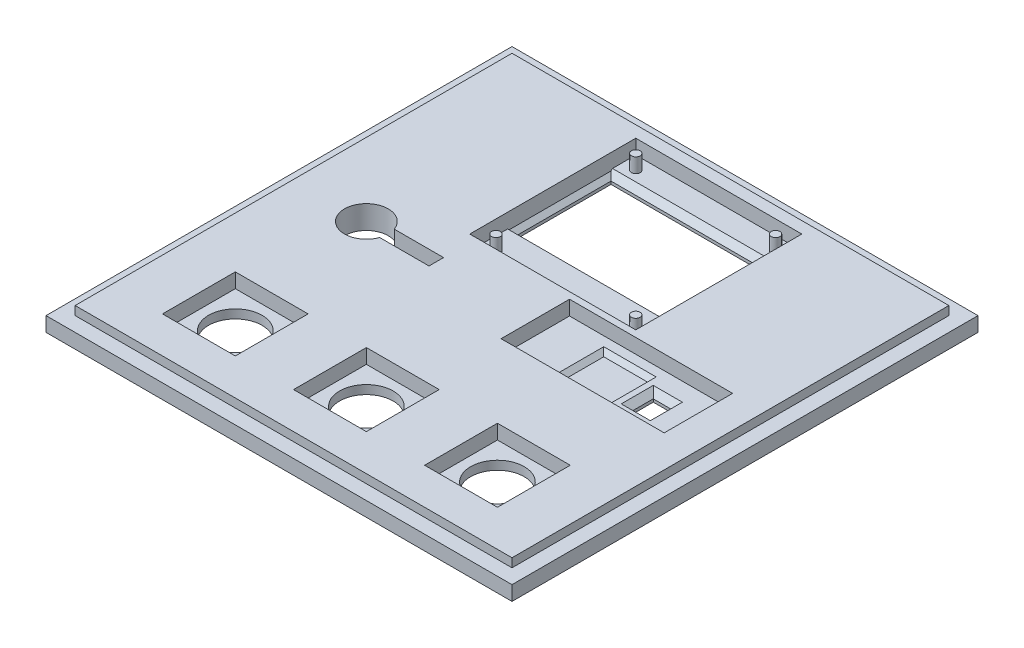
SolidWorks part; units mm, degrees
ref_plane "Ebene vorne" through (0, 0, 0) normal (0, 0, 1) x (1, 0, 0)
ref_plane "Ebene oben" through (0, 0, 0) normal (0, 1, 0) x (1, 0, 0)
ref_plane "Ebene rechts" through (0, 0, 0) normal (1, 0, 0) x (0, 0, -1)
sketch "Sketch1" plane through (0, 0, 0) normal (0, 1, 0) x (1, 0, 0)
  line L0 (0, -1000) -> (0, 49000) construction
  line L1 (-40, -40) -> (40, -40)
  line L2 (-40, -40) -> (-40, 40)
  line L3 (-40, 40) -> (40, 40)
  line L4 (40, -40) -> (40, 40)
  line L5 (-40, -40) -> (40, 40) construction
  line L6 (-40, 40) -> (40, -40) construction
  line L7 (-13.5, 30.5) -> (13.5, 30.5)
  line L8 (-13.5, 30.5) -> (-13.5, 14.5)
  line L9 (-13.5, 14.5) -> (13.5, 14.5)
  line L10 (13.5, 30.5) -> (13.5, 14.5)
  line L11 (-13.5, 30.5) -> (13.5, 14.5) construction
  line L12 (-13.5, 14.5) -> (13.5, 30.5) construction
  line L13 (22.5, 1.75) -> (25.5, 1.75)
  line L14 (22.5, 1.75) -> (22.5, -1.75)
  line L15 (22.5, -1.75) -> (25.5, -1.75)
  line L16 (25.5, 1.75) -> (25.5, -1.75)
  line L17 (22.5, 1.75) -> (25.5, -1.75) construction
  line L18 (22.5, -1.75) -> (25.5, 1.75) construction
  line L20 (-25.75, -28.25) -> (-19.25, -28.25) construction
  line L21 (-25.75, -28.25) -> (-25.75, -21.75) construction
  line L22 (-25.75, -21.75) -> (-19.25, -21.75) construction
  line L23 (-19.25, -28.25) -> (-19.25, -21.75) construction
  line L24 (-25.75, -28.25) -> (-19.25, -21.75) construction
  line L25 (-25.75, -21.75) -> (-19.25, -28.25) construction
  circle A0 centre (-25, 0) radius 3.75
  circle A1 centre (-22.5, -25) radius 4.5962
  circle A2 centre (0, -25) radius 4.5962
  circle A3 centre (22.5, -25) radius 4.5962
  point P0 (0, 0)
  point P8 (0, 22.5)
  point P13 (24, 0)
  dimension "D1" = 7.5
  dimension "D9" = 6.5
  dimension "D2" = 25
  dimension "D3" = 27
  dimension "D4" = 16
  dimension "D5" = 22.5
  dimension "D6" = 3.5
  dimension "D7" = 3
  dimension "D8" = 24
  dimension "D10" = 6.5
  dimension "D11" = 25
  dimension "D12" = 45
  dimension "D13" = 80
  dimension "D14" = 80
extrude "Boss-Extrude1" add sketch "Sketch1" along normal blind 2.5
sketch "Sketch2" plane through (0, 2.5, 0) normal (0, 1, 0) x (1, 0, 0)
  line L14 (-37.5, -37.5) -> (37.5, -37.5)
  line L15 (37.5, -37.5) -> (37.5, 37.5)
  line L16 (37.5, 37.5) -> (-37.5, 37.5)
  line L17 (-37.5, 37.5) -> (-37.5, -37.5)
  line L18 (-37.5, -37.5) -> (37.5, -37.5)
  line L19 (37.5, -37.5) -> (37.5, 37.5)
  line L20 (37.5, 37.5) -> (-37.5, 37.5)
  line L21 (-37.5, 37.5) -> (-37.5, -37.5)
  line L60 (-13.5, 14.5) -> (13.5, 14.5) construction
  line L65 (-13.5, 30.5) -> (-13.5, 14.5) construction
  line L71 (13.5, 30.5) -> (-13.5, 30.5) construction
  line L78 (13.5, 14.5) -> (13.5, 30.5) construction
  line L94 (-13.5, 14.5) -> (13.5, 14.5)
  line L95 (13.5, 14.5) -> (13.5, 30.5)
  line L96 (13.5, 30.5) -> (-13.5, 30.5)
  line L97 (-13.5, 30.5) -> (-13.5, 14.5)
  line L106 (25.5, 1.75) -> (22.5, 1.75)
  line L107 (25.5, -1.75) -> (25.5, 1.75)
  line L108 (22.5, -1.75) -> (25.5, -1.75)
  line L109 (22.5, 1.75) -> (22.5, -1.75)
  line L110 (25.5, 1.75) -> (22.5, 1.75)
  line L111 (25.5, -1.75) -> (25.5, 1.75)
  line L112 (22.5, -1.75) -> (25.5, -1.75)
  line L113 (22.5, 1.75) -> (22.5, -1.75)
  circle A65 centre (-25, 0) radius 3.75
  circle A66 centre (-25, 0) radius 3.75
  circle A68 centre (-22.5, -25) radius 4.5962
  circle A69 centre (-22.5, -25) radius 4.5962
  circle A71 centre (0, -25) radius 4.5962
  circle A72 centre (0, -25) radius 4.5962
  circle A74 centre (22.5, -25) radius 4.5962
  circle A75 centre (22.5, -25) radius 4.5962
  dimension "D1" = 2.5
  dimension "D2" = 0
  dimension "D3" = 0
  dimension "D4" = 0
  dimension "D5" = 0
  dimension "D6" = 0
extrude "Boss-Extrude2" add sketch "Sketch2" along normal blind 1.5
sketch "Sketch3" plane through (0, 4, 0) normal (0, 1, 0) x (1, 0, 0)
  line L0 (-1000.1223, 0) -> (48999.8777, 0) construction
  line L1 (32, 5.875) -> (4, 5.875)
  line L2 (32, 5.875) -> (32, -5.875)
  line L3 (32, -5.875) -> (4, -5.875)
  line L4 (4, 5.875) -> (4, -5.875)
  line L5 (25.5, -1.75) -> (25.5, 1.75) construction
  line L7 (-28.75, -31.25) -> (-16.25, -31.25)
  line L8 (-28.75, -31.25) -> (-28.75, -18.75)
  line L9 (-28.75, -18.75) -> (-16.25, -18.75)
  line L10 (-16.25, -31.25) -> (-16.25, -18.75)
  line L11 (-28.75, -31.25) -> (-16.25, -18.75) construction
  line L12 (-28.75, -18.75) -> (-16.25, -31.25) construction
  line L13 (-6.25, -31.25) -> (6.25, -31.25)
  line L14 (-6.25, -31.25) -> (-6.25, -18.75)
  line L15 (-6.25, -18.75) -> (6.25, -18.75)
  line L16 (6.25, -31.25) -> (6.25, -18.75)
  line L17 (-6.25, -31.25) -> (6.25, -18.75) construction
  line L18 (-6.25, -18.75) -> (6.25, -31.25) construction
  line L19 (28.75, -31.25) -> (16.25, -31.25)
  line L20 (28.75, -31.25) -> (28.75, -18.75)
  line L21 (28.75, -18.75) -> (16.25, -18.75)
  line L22 (16.25, -31.25) -> (16.25, -18.75)
  line L23 (28.75, -31.25) -> (16.25, -18.75) construction
  line L24 (28.75, -18.75) -> (16.25, -31.25) construction
  line L25 (-14.25, 35.5) -> (14.25, 35.5)
  line L26 (-14.25, 35.5) -> (-14.25, 7)
  line L27 (-14.25, 7) -> (14.25, 7)
  line L28 (14.25, 35.5) -> (14.25, 7)
  line L31 (13.5, 30.5) -> (-13.5, 30.5) construction
  line L32 (0, -1000) -> (0, 49000) construction
  line L33 (-1031.2728, 21.25) -> (48968.7272, 21.25) construction
  line L34 (-25, -1.25) -> (-13, -1.25)
  line L35 (-25, -1.25) -> (-25, 1.25)
  line L36 (-25, 1.25) -> (-13, 1.25)
  line L37 (-13, -1.25) -> (-13, 1.25)
  line L38 (-25, -1.25) -> (-13, 1.25) construction
  line L39 (-25, 1.25) -> (-13, -1.25) construction
  circle A0 centre (-12, 9.25) radius 0.75
  circle A1 centre (12, 9.25) radius 0.75
  circle A2 centre (-12, 33.25) radius 0.75
  circle A3 centre (12, 33.25) radius 0.75
  circle A5 centre (-25, 0) radius 3.75 construction
  point P9 (-22.5, -25)
  point P15 (0, -25)
  point P21 (22.5, -25)
  point P48 (-19, 0)
  dimension "D9" = 1.5
  dimension "D14" = 12
  dimension "D1" = 11.75
  dimension "D2" = 28
  dimension "D3" = 6.5
  dimension "D4" = 12.5
  dimension "D5" = 28.5
  dimension "D7" = 5
  dimension "D8" = 28.5
  dimension "D10" = 24
  dimension "D11" = 24
  dimension "D12" = 2.5
  dimension "D13" = 0
extrude "Cut-Extrude1" cut sketch "Sketch3" against normal blind 2.5
sketch "Sketch5" plane through (0, 0, 0) normal (0, -1, 0) x (1, 0, 0)
  line L0 (-1025, 0) -> (48975, 0) construction
  line L1 (-25, -1000) -> (-25, 49000) construction
  text T0 "<b><r180>n O</r></b>"
  text T1 "<b><r180>ff  O</r></b>"
  dimension "D1" = 10
  dimension "D2" = 10
extrude "Cut-Extrude2" cut sketch "Sketch5" against normal blind 1
chamfer "Chamfer1" distance 1 angle 45 8 edges at (0, 1.5, -14.5) (13.5, 1.5, -22.5) (0, 1.5, -30.5) (-13.5, 1.5, -22.5) (24, 1.5, 1.75) (22.5, 1.5, 0) (24, 1.5, -1.75) (25.5, 1.5, 0)
sketch "Sketch6" plane through (0, 1.5, 0) normal (0, 1, 0) x (1, 0, 0)
  line L0 (22.5, 1.75) -> (22.5, -1.75) construction
  line L1 (12.5, -3.25) -> (19.5, -3.25)
  line L2 (12.5, -3.25) -> (12.5, 3.25)
  line L3 (12.5, 3.25) -> (19.5, 3.25)
  line L4 (19.5, -3.25) -> (19.5, 3.25)
  line L5 (12.5, -3.25) -> (19.5, 3.25) construction
  line L6 (12.5, 3.25) -> (19.5, -3.25) construction
  point P0 (16, 0)
  dimension "D1" = 6.5
  dimension "D2" = 3
  dimension "D3" = 10
extrude "Cut-Extrude3" cut sketch "Sketch6" against normal blind 0.75
chamfer "Chamfer2" distance 1 angle 45 4 edges at (16, 1.5, 3.25) (12.5, 1.5, 0) (16, 1.5, -3.25) (19.5, 1.5, 0)
